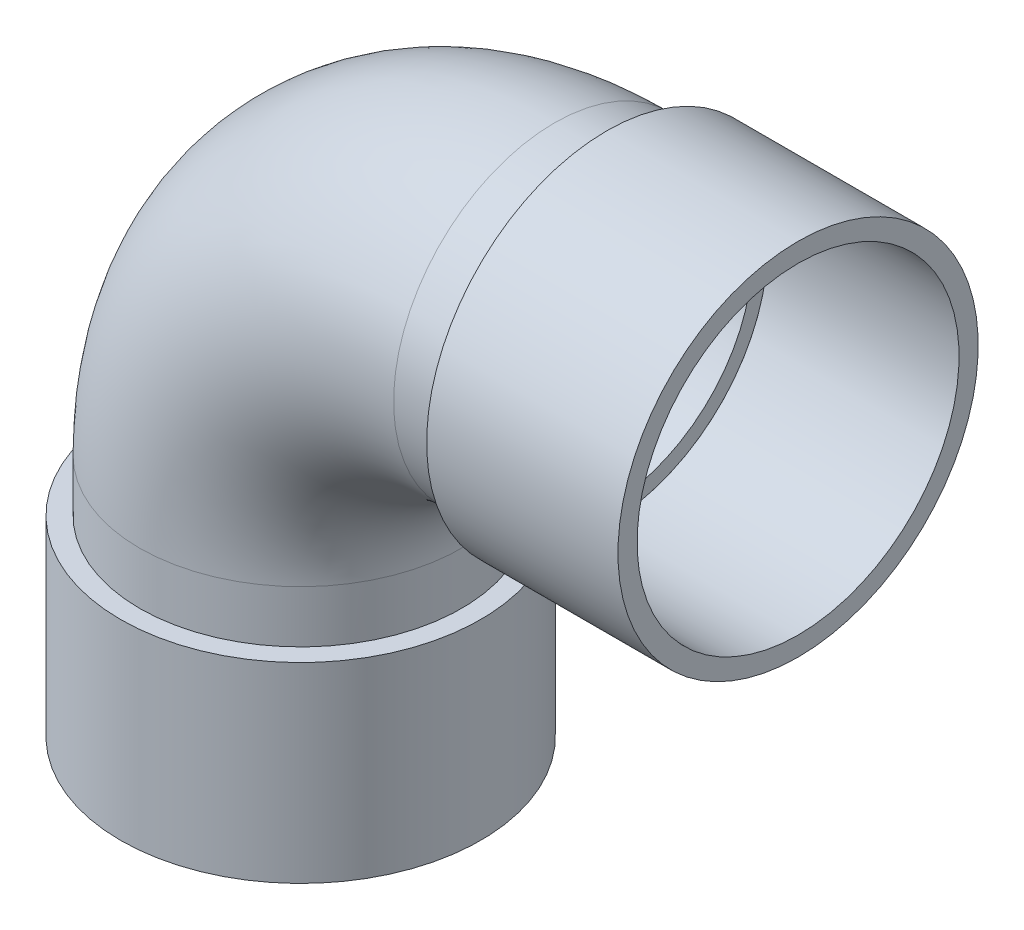
SolidWorks part; units mm, degrees
material "PVC Rígido"
ref_plane "Alzado" through (0, 0, 0) normal (0, 0, 1) x (1, 0, 0)
ref_plane "Planta" through (0, 0, 0) normal (0, 1, 0) x (1, 0, 0)
ref_plane "Vista lateral" through (0, 0, 0) normal (1, 0, 0) x (0, 0, -1)
sketch "Croquis2" plane through (0, 0, 0) normal (0, 0, 1) x (1, 0, 0)
  line L0 (0, 0) -> (0, 27.27)
  line L1 (132.73, 160) -> (160, 160)
  arc A0 (0, 27.27) -> (132.73, 160) centre (132.73, 27.27) cw
  point P6 (0, 160)
  point P9 (0, 160)
  dimension "D3" = 132.73
  dimension "D1" = 160
  dimension "D2" = 160
sketch "Croquis3" plane through (0, 0, 0) normal (0, 1, 0) x (1, 0, 0)
  circle A0 centre (0, 0) radius 84.15
  circle A1 centre (0, 0) radius 76.2
  dimension "D1" = 168.3
  dimension "D2" = 152.4
sweep "Barrer1" add profiles "Croquis3" path "Croquis2"
sketch "Croquis4" plane through (160, 0, 0) normal (1, 0, 0) x (0, 0, -1)
  circle A0 centre (0, 160) radius 94.15
  circle A1 centre (0, 160) radius 84.15
  circle A2 centre (0, 160) radius 84.15
  dimension "D2" = 10
  dimension "D1" = 0
extrude "Saliente-Extruir1" add sketch "Croquis4" along normal blind 100 separate body
sketch "Croquis5" plane through (0, 0, 0) normal (0, -1, 0) x (1, 0, 0)
  circle A0 centre (0, 0) radius 94.15
  circle A1 centre (0, 0) radius 84.15
  circle A2 centre (0, 0) radius 84.15
  dimension "D2" = 10
  dimension "D1" = 0
extrude "Saliente-Extruir2" add sketch "Croquis5" along normal blind 100 separate body
